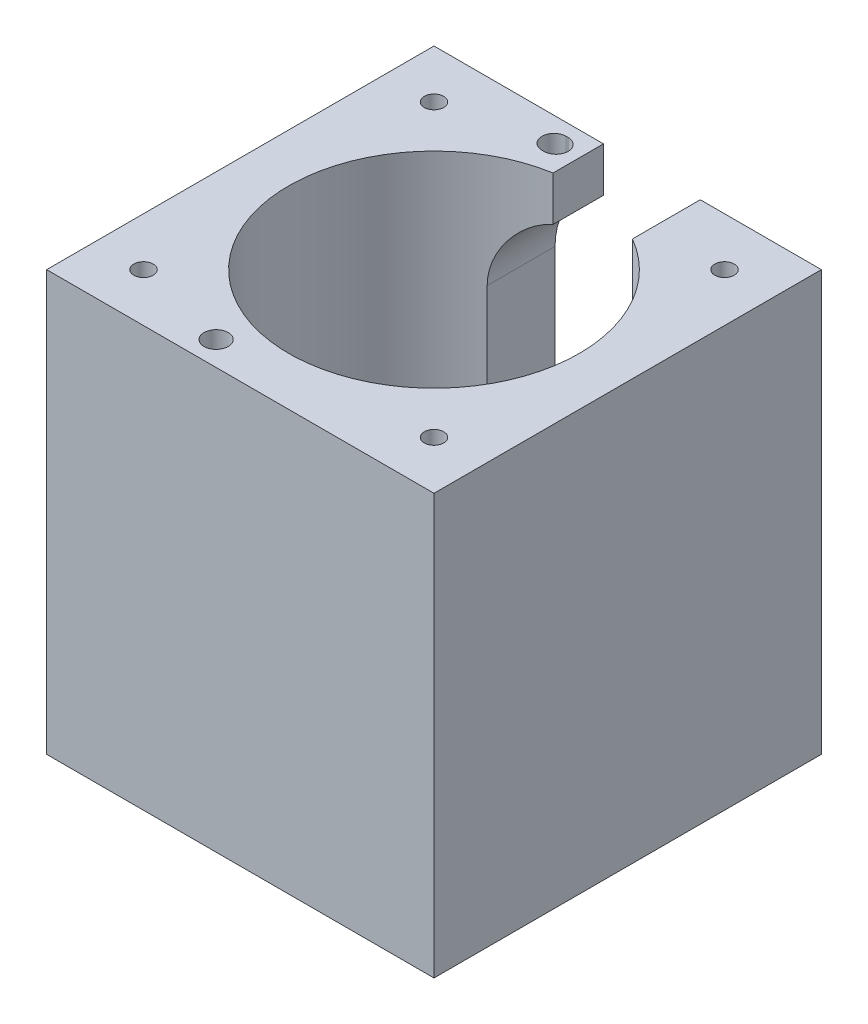
SolidWorks part; units mm, degrees
ref_plane "XY" through (0, 0, 0) normal (0, 0, 1) x (1, 0, 0)
ref_plane "XZ" through (0, 0, 0) normal (0, 1, 0) x (1, 0, 0)
ref_plane "YZ" through (0, 0, 0) normal (1, 0, 0) x (0, 0, -1)
ref_axis "X" through (-55.88, 0, 0) along (1, 0, 0)
ref_axis "Y" through (0, -10.3314, 0) along (0, 1, 0)
ref_axis "Z" through (0, 0, 55.88) along (0, 0, -1)
sketch "Sketch1" plane through (0, 0, 0) normal (0, 1, 0) x (1, 0, 0)
  line L1 (-50.8, -50.8) -> (50.8, -50.8)
  line L2 (-50.8, -50.8) -> (-50.8, 50.8)
  line L3 (-50.8, 50.8) -> (50.8, 50.8)
  line L4 (50.8, -50.8) -> (50.8, 50.8)
  line L5 (-50.8, -50.8) -> (50.8, 50.8) construction
  line L6 (-50.8, 50.8) -> (50.8, -50.8) construction
  circle A0 centre (0, 0) radius 38.1
  point P0 (0, 0)
  dimension "D2" = 76.2
  dimension "D1" = 101.6
extrude "Boss-Extrude1" add sketch "Sketch1" along normal blind 105.283
sketch "Sketch2" plane through (0, 0, 0) normal (0, -1, 0) x (1, 0, 0)
  line L4 (50.8, -50.8) -> (50.8, 50.8)
  line L5 (50.8, 50.8) -> (-50.8, 50.8)
  line L6 (-50.8, 50.8) -> (-50.8, -50.8)
  line L7 (-50.8, -50.8) -> (50.8, -50.8)
  line L8 (50.8, -50.8) -> (50.8, 50.8)
  line L9 (50.8, 50.8) -> (-50.8, 50.8)
  line L10 (-50.8, 50.8) -> (-50.8, -50.8)
  line L11 (-50.8, -50.8) -> (50.8, -50.8)
  circle A0 centre (0, 0) radius 20.5
  dimension "D2" = 41
  dimension "D1" = 0
extrude "Boss-Extrude2" add sketch "Sketch2" along normal blind 4.826
hole_wizard "M5 Clearance Hole1" positions "Sketch3" profile "Sketch4" hole size "M5" standard "ANSI Metric" end condition through all
sketch "Sketch3" plane through (0, -4.826, 0) normal (0, -1, 0) x (-1, 0, 0)
  circle A0 centre (0, 0) radius 26
  point P0 (26, 0)
  point P7 (0, -26)
  point P9 (-26, 0)
  point P11 (0, 26)
  point P14 (26, 0)
  point P15 (0, 0)
  dimension "D1" = 52
sketch "Sketch4" plane through (-26, -4.826, 0) normal (1, 0, 0) x (0, 0, -1)
  line L0 (0, 0) -> (0, 110.109)
  line L1 (0, 110.109) -> (2.75, 110.109)
  line L2 (2.75, 110.109) -> (2.75, 0)
  line L5 (2.75, 0) -> (0, 0)
  line L11 (0, -6.35) -> (0, 107.95) construction
  dimension "Thru Hole Dia." = 5.5
  dimension "Thru Hole Depth" = 110.109
hole_wizard "1/4-20 Tapped Hole1" positions "Sketch5" profile "Sketch6" tap size "1/4-20" standard "ANSI Inch"
sketch "Sketch5" plane through (0, 105.283, 0) normal (0, 1, 0) x (1, 0, 0)
  line L2 (-38.1, -38.1) -> (38.1, -38.1)
  line L3 (-38.1, -38.1) -> (-38.1, 38.1)
  line L4 (-38.1, 38.1) -> (38.1, 38.1)
  line L5 (38.1, -38.1) -> (38.1, 38.1)
  line L6 (0, -38.1) -> (0, 0) construction
  line L7 (0, 0) -> (-38.1, 0) construction
  point P121 (-38.1, -38.1)
  point P122 (38.1, 38.1)
  point P241 (-38.1, 38.1)
  point P242 (38.1, -38.1)
  dimension "D1" = 76.2
sketch "Sketch6" plane through (-38.1, 105.283, 38.1) normal (1, 0, 0) x (0, 0, 1)
  line L0 (0, 0) -> (0, 18.0438)
  line L1 (0, 18.0438) -> (2.5527, 16.51)
  line L2 (2.5527, 16.51) -> (2.5527, 0)
  line L5 (2.5527, 0) -> (0, 0)
  line L10 (0, 18.0438) -> (-2.5527, 16.51) construction
  line L11 (0, -6.35) -> (0, 107.95) construction
  dimension "Tap Drill Dia." = 5.1054
  dimension "Tap Drill Depth" = 16.51
  dimension "Drill Angle" = 118
cosmetic thread "Hole Thread1" parameters "D1"=12.7, "D2"=6.35
cosmetic thread "Hole Thread2" parameters "D1"=12.7, "D2"=6.35
cosmetic thread "Hole Thread3" parameters "D1"=12.7, "D2"=6.35
cosmetic thread "Hole Thread4" parameters "D1"=12.7, "D2"=6.35
hole_wizard "1/4 (0.2500) Dowel Hole1" positions "Sketch7" profile "Sketch8" hole size "1/4" standard "ANSI Inch"
sketch "Sketch7" plane through (0, 105.283, 0) normal (0, 1, 0) x (1, 0, 0)
  line L0 (-12.7, 44.45) -> (-12.7, -44.45)
  line L2 (0, 0) -> (-12.7, 0) construction
  point P0 (-12.7, -44.45)
  dimension "D1" = 88.9
  dimension "D2" = 12.7
sketch "Sketch8" plane through (-12.7, 105.283, 44.45) normal (1, 0, 0) x (0, 0, 1)
  line L0 (0, 0) -> (0, 18.4177)
  line L1 (0, 18.4177) -> (3.175, 16.51)
  line L2 (3.175, 16.51) -> (3.175, 0)
  line L5 (3.175, 0) -> (0, 0)
  line L10 (0, 18.4177) -> (-3.175, 16.51) construction
  line L11 (0, -6.35) -> (0, 107.95) construction
  dimension "Hole Dia." = 6.35
  dimension "Hole Depth" = 16.51
  dimension "Drill Angle" = 118
hole_wizard "1/4 (0.2500) Dowel Slot1" positions "Sketch9" profile "Sketch10" size "1/4" standard "ANSI Inch" slot yes
sketch "Sketch9" plane through (0, 105.283, 0) normal (0, 1, 0) x (1, 0, 0)
  line L0 (-16.129, 44.45) -> (-9.271, 44.45) construction
  point P0 (-12.7, 44.45)
  point P5 (0, 44.45)
  dimension "D1" = 6.858
sketch "Sketch10" plane through (-12.7, 105.283, -44.45) normal (1, 0, 0) x (0, 0, 1)
  line L0 (0, 0) -> (0, 18.4177)
  line L1 (0, 18.4177) -> (3.175, 16.51)
  line L2 (3.175, 16.51) -> (3.175, 0)
  line L5 (3.175, 0) -> (0, 0)
  line L10 (0, 18.4177) -> (-3.175, 16.51) construction
  line L11 (0, -6.35) -> (0, 107.95) construction
  dimension "Hole Dia." = 6.35
  dimension "Hole Depth" = 16.51
  dimension "Drill Angle" = 118
chamfer "Chamfer1" distance 0.254 angle 45 1 edges at (0, -4.826, -20.5)
sketch "Sketch12" plane through (0, 105.283, 0) normal (0, 1, 0) x (1, 0, 0)
  line L0 (-50.8, 50.8) -> (-50.8, -50.8) construction
  line L1 (50.8, 25.4) -> (-50.8, 25.4)
  line L2 (50.8, 25.4) -> (50.8, -25.4)
  line L3 (50.8, -25.4) -> (-50.8, -25.4)
  line L4 (-50.8, 25.4) -> (-50.8, -25.4)
  line L5 (50.8, 25.4) -> (-50.8, -25.4) construction
  line L6 (50.8, -25.4) -> (-50.8, 25.4) construction
  point P0 (0, 0)
  dimension "D1" = 50.8
sketch "Sketch13" plane through (0, 0, -50.8) normal (0, 0, -1) x (-1, 0, 0)
  line L0 (0, 24.8285) -> (0, 75.6285) construction
  line L1 (-19.05, 24.8285) -> (-19.05, 75.6285)
  line L2 (19.05, 24.8285) -> (19.05, 75.6285)
  line L3 (0, 50.2285) -> (-50.8, 50.2285) construction
  line L4 (-50.8, 105.283) -> (-50.8, -4.826) construction
  arc A0 (-19.05, 24.8285) -> (19.05, 24.8285) centre (0, 24.8285) ccw
  arc A1 (19.05, 75.6285) -> (-19.05, 75.6285) centre (0, 75.6285) ccw
  point P2 (0, 50.2285)
  dimension "D2" = 19.05
  dimension "D1" = 50.8
extrude "Cut-Extrude2" cut sketch "Sketch13" against normal up to next
sketch "Sketch14" plane through (0, 0, -50.8) normal (0, 0, -1) x (-1, 0, 0)
  line L1 (-19.05, 75.6285) -> (6.35, 75.6285)
  line L2 (-19.05, 75.6285) -> (-19.05, 105.283)
  line L3 (-19.05, 105.283) -> (6.35, 105.283)
  line L4 (6.35, 75.6285) -> (6.35, 105.283)
  line L5 (-50.8, 105.283) -> (50.8, 105.283) construction
  line L6 (-19.05, 75.6285) -> (-19.05, 24.8285) construction
  point P4 (0, 105.283)
  point P5 (-6.2041, 105.283)
  point P6 (0, 0)
  point P7 (0, 0)
  point P12 (0, 0)
  point P15 (0, 0)
  point P16 (-12.7, 75.6285)
  dimension "D3" = 6.35
extrude "Cut-Extrude3" cut sketch "Sketch14" against normal up to next
